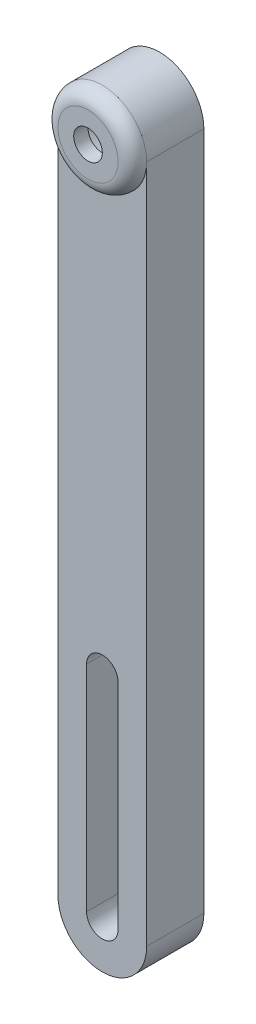
SolidWorks part; units mm, degrees
ref_plane "Front Plane" through (0, 0, 0) normal (0, 0, 1) x (1, 0, 0)
ref_plane "Top Plane" through (0, 0, 0) normal (0, 1, 0) x (1, 0, 0)
ref_plane "Right Plane" through (0, 0, 0) normal (1, 0, 0) x (0, 0, -1)
sketch "Sketch1" plane through (0, 0, 0) normal (0, 0, 1) x (1, 0, 0)
  line L0 (-8.7776, 7.123) -> (-8.7776, -40.377) construction
  line L1 (-5.6776, 7.123) -> (-5.6776, -40.377)
  line L2 (-11.8776, 7.123) -> (-11.8776, -40.377)
  line L3 (-8.7776, -25.377) -> (-8.7776, -40.377) construction
  line L4 (-7.6776, -25.377) -> (-7.6776, -40.377)
  line L5 (-9.8776, -25.377) -> (-9.8776, -40.377)
  arc A0 (-5.6776, 7.123) -> (-11.8776, 7.123) centre (-8.7776, 7.123) ccw
  arc A1 (-11.8776, -40.377) -> (-5.6776, -40.377) centre (-8.7776, -40.377) ccw
  circle A5 centre (-8.7776, 7.123) radius 2.5
  arc A6 (-7.6776, -25.377) -> (-9.8776, -25.377) centre (-8.7776, -25.377) ccw
  arc A7 (-9.8776, -40.377) -> (-7.6776, -40.377) centre (-8.7776, -40.377) ccw
  point P2 (-8.7776, -16.627)
  point P11 (-8.7776, -32.877)
  dimension "D1" = 3.1
  dimension "D3" = 5
  dimension "D6" = 2
  dimension "D4" = 1.1
  dimension "D2" = 47.5
  dimension "D5" = 6.2
  dimension "D7" = 15
extrude "Boss-Extrude1" add sketch "Sketch1" along normal blind 4
sketch "Sketch2" plane through (0, 0, 4) normal (0, 0, 1) x (1, 0, 0)
  circle A1 centre (-8.7776, 7.123) radius 1
  circle A2 centre (-8.7776, 7.123) radius 3.1
  dimension "D1" = 2
extrude "Boss-Extrude2" add sketch "Sketch2" along normal blind 1 separate body
fillet "Fillet1" radius 1 1 edges at (-5.6776, 7.123, 5)
